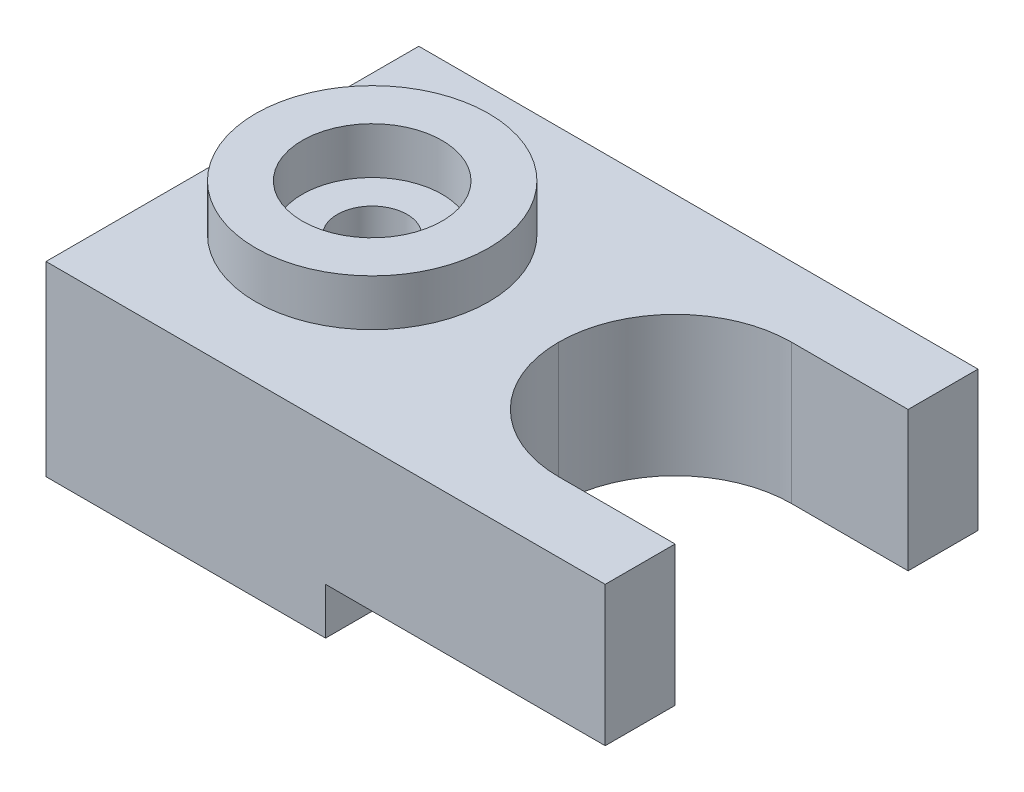
SolidWorks part; units mm, degrees
ref_plane "Front Plane" through (0, 0, 0) normal (0, 0, 1) x (1, 0, 0)
ref_plane "Top Plane" through (0, 0, 0) normal (0, 1, 0) x (1, 0, 0)
ref_plane "Right Plane" through (0, 0, 0) normal (1, 0, 0) x (0, 0, -1)
sketch "Sketch2" plane through (0, 0, 0) normal (0, 0, 1) x (1, 0, 0)
  line L1 (-38.1, -12.7) -> (38.1, -12.7)
  line L2 (-38.1, -12.7) -> (-38.1, 12.7)
  line L3 (-38.1, 12.7) -> (38.1, 12.7)
  line L4 (38.1, -12.7) -> (38.1, 12.7)
  line L5 (-38.1, -12.7) -> (38.1, 12.7) construction
  line L6 (-38.1, 12.7) -> (38.1, -12.7) construction
  point P0 (0, 0)
  dimension "D1" = 76.2
  dimension "D2" = 25.4
extrude "Boss-Extrude1" add sketch "Sketch2" along normal mid plane 50.8
sketch "Sketch3" plane through (0, 0, 25.4) normal (0, 0, 1) x (1, 0, 0)
  line L1 (38.1, -12.7) -> (0, -12.7)
  line L2 (38.1, -12.7) -> (38.1, -6.35)
  line L3 (38.1, -6.35) -> (0, -6.35)
  line L4 (0, -12.7) -> (0, -6.35)
  line L5 (38.1, -12.7) -> (0, -6.35) construction
  line L6 (38.1, -6.35) -> (0, -12.7) construction
  point P4 (19.05, -9.525)
  dimension "D1" = 38.1
  dimension "D2" = 6.35
extrude "Cut-Extrude1" cut sketch "Sketch3" against normal through all
sketch "Sketch4" plane through (0, 0, 0) normal (0, 1, 0) x (1, 0, 0)
  line L0 (38.1, -25.4) -> (38.1, 25.4) construction
  line L1 (38.1, -15.875) -> (6.35, -15.875)
  line L2 (38.1, -15.875) -> (38.1, 15.875)
  line L3 (38.1, 15.875) -> (6.35, 15.875)
  line L4 (6.35, -15.875) -> (6.35, 15.875)
  line L5 (38.1, -15.875) -> (6.35, 15.875) construction
  line L6 (38.1, 15.875) -> (6.35, -15.875) construction
  point P4 (22.225, 0)
  dimension "D1" = 31.75
  dimension "D2" = 31.75
  dimension "D3" = 0
extrude "Cut-Extrude2" cut sketch "Sketch4" against normal through all and the other way through all
fillet "Fillet2" radius 15.875 2 edges at (6.35, 3.175, 15.875) (6.35, 3.175, -15.875)
sketch "Sketch5" plane through (0, 12.7, 0) normal (0, 1, 0) x (1, 0, 0)
  circle A0 centre (-19.05, 0) radius 15.875
  arc A1 (6.35, 0) -> (22.225, -15.875) centre (22.225, 0) ccw construction
  point P2 (0, 0)
  dimension "D1" = 41.275
  dimension "D2" = 31.75
  dimension "D3" = 0
extrude "Boss-Extrude2" add sketch "Sketch5" along normal blind 6.35
hole_wizard "Hole1" positions "3DSketch1" profile "Sketch6" legacy end condition through all
sketch3d "3DSketch1"
  line L0 (-19.05, 19.05, 0) -> (-19.05, 12.7, 0) construction
  point P0 (-19.05, 19.05, 0)
  point P4 (-19.05, 19.05, 0)
sketch "Sketch6" plane through (-19.05, 19.05, 0) normal (1, 0, 0) x (0, 0, 1)
  line L0 (0, 0) -> (0, 34.6116)
  line L1 (0, 34.6116) -> (4.7625, 31.75)
  line L2 (4.7625, 31.75) -> (4.7625, 6.35)
  line L3 (4.7625, 6.35) -> (9.525, 6.35)
  line L4 (9.525, 0) -> (0, 0)
  line L5 (0, -11.3109) -> (0, 121.1557) construction
  line L6 (0, 34.6116) -> (-4.7625, 31.75) construction
  line L7 (9.525, 6.35) -> (9.525, 0)
  dimension "Depth" = 31.75
  dimension "Drill Angle" = 118
  dimension "Diameter" = 9.525
  dimension "C-Bore Diameter" = 19.05
  dimension "C-Bore Depth" = 6.35
